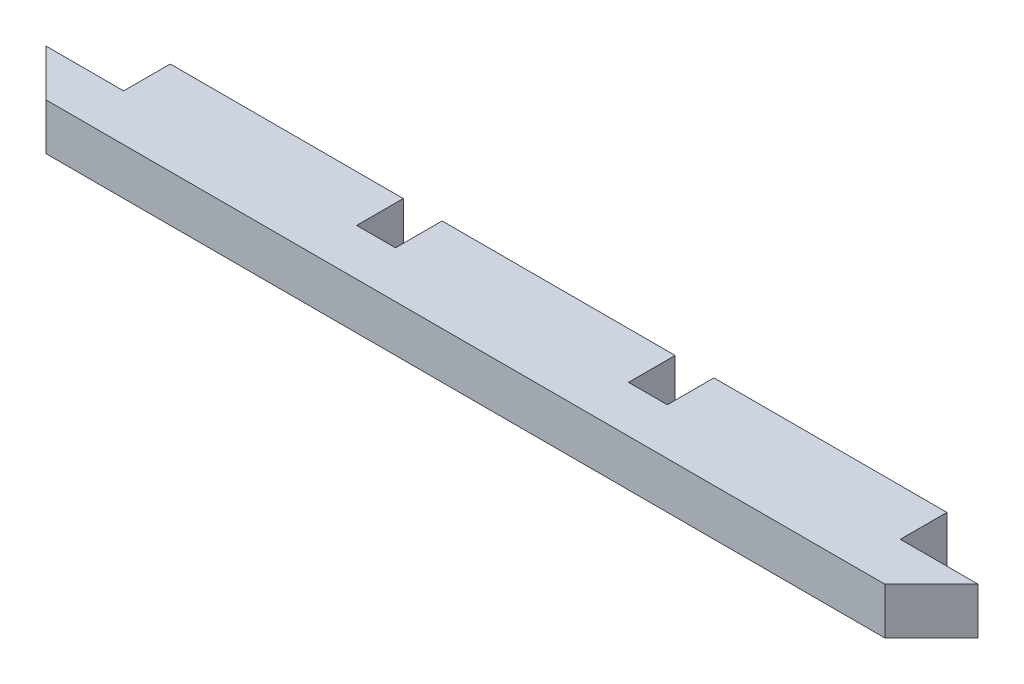
SolidWorks part; units mm, degrees
ref_plane "Front Plane" through (0, 0, 0) normal (0, 0, 1) x (1, 0, 0)
ref_plane "Top Plane" through (0, 0, 0) normal (0, 1, 0) x (1, 0, 0)
ref_plane "Right Plane" through (0, 0, 0) normal (1, 0, 0) x (0, 0, -1)
sketch "Sketch1" plane through (0, 0, 0) normal (0, 1, 0) x (1, 0, 0)
  line L0 (-60, 3) -> (0, -57)
  line L1 (-60, 3) -> (60, 3)
  line L2 (-60, 3) -> (-60, -3)
  line L3 (-60, -3) -> (60, -3)
  line L4 (60, 3) -> (60, -3)
  line L5 (-60, 3) -> (60, -3) construction
  line L6 (-60, -3) -> (60, 3) construction
  line L7 (0, -57) -> (60, 3)
  line L8 (0, -57) -> (0, -3) construction
  point P0 (0, 0)
  point P6 (0, -3)
  dimension "D1" = 6
  dimension "D2" = 120
sketch "Sketch2" plane through (0, 0, 0) normal (0, 0, 1) x (1, 0, 0)
  line L0 (0, 0) -> (0, 6) construction
  line L1 (-60, 0) -> (60, 0) construction
  point P4 (0, 3)
  dimension "D1" = 6
extrude "Boss-Extrude1" add sketch "Sketch1" along normal up to vertex (6 mm away) contours L3 L7 L1 L0 region at (0, 0, -0.0526) up to point (0, 6, 0)
sketch "Sketch3" plane through (0, 0, 0) normal (0, -1, 0) x (1, 0, 0)
  line L0 (43, -9) -> (25, -9) construction
  line L1 (50, -3) -> (20, -3)
  line L2 (50, -3) -> (50, -9)
  line L3 (50, -9) -> (20, -9)
  line L4 (20, -3) -> (20, -9)
  line L5 (-43, -9) -> (-25, -9) construction
  line L6 (-50, -3) -> (-20, -3)
  line L7 (-50, -3) -> (-50, -9)
  line L8 (-50, -9) -> (-20, -9)
  line L9 (-20, -3) -> (-20, -9)
  line L10 (-60, -3) -> (60, -3) construction
  line L11 (15, -3) -> (-15, -3)
  line L12 (15, -3) -> (15, -9)
  line L13 (15, -9) -> (-15, -9)
  line L14 (-15, -3) -> (-15, -9)
  line L15 (-25, -9) -> (-9, -9) construction
  line L16 (0, -3) -> (0, 0) construction
  line L17 (-50, -3) -> (-60, -3)
  line L18 (50, -3) -> (60, -3)
  line M7 (-60, -3) -> (60, -3)
  dimension "D1" = 30
  dimension "D2" = 10
extrude "Boss-Extrude2" add sketch "Sketch3" against normal up to surface (6 mm away) contours L4 L3 L2 M7 | L14 L13 L12 L11 M7 | L9 L7 L8 M7 region at (35, 0, -6) region at (-35, 0, -6) region at (0, 0, -6) up to face at (0, 6, 0)
equation "\"glass_width\"= 150"
equation "\"glass_height\"= 100"
equation "\"glass_thickness\"= 4"
equation "\"brood_space\"= 42"
equation "\"t1\"= 6"
equation "\"t2\"= 6"
equation "\"box_depth\"= \"brood_space\" + \"glass_thickness\" + \"glass_thickness\" + \"t2\" + \"t2\""
equation "\"box_width\"= \"glass_width\" + \"t1\" + \"t1\""
equation "\"food_height\"= 70"
equation "\"box_height\"= \"glass_height\" + ( \"t1\" * 3 ) + \"food_height\""
equation "\"D2@Sketch1\"=\"glass_width\"-30"
equation "\"D1@Sketch2\"=\"t2\""
equation "\"entry_height\"= 24"
equation "\"entry_diameter\"= 8"
equation "\"food_top_clearance\"= 10"
equation "\"bar_width\"= 20"
equation "\"glassblocker_lower_height\"= 10"
equation "\"lower_edge_stickout\"=6"
